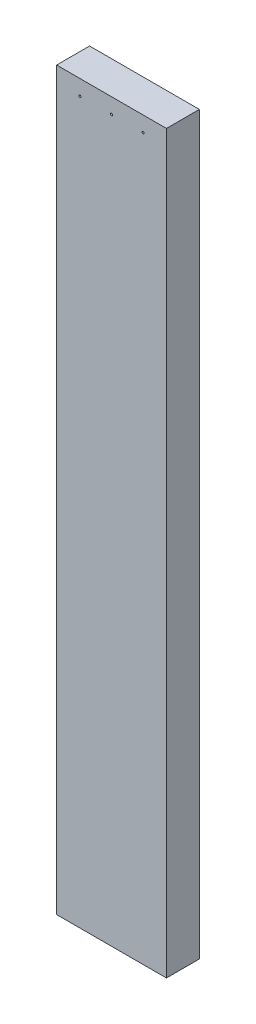
SolidWorks part; units mm, degrees
ref_plane "Front Plane" through (0, 0, 0) normal (0, 0, 1) x (1, 0, 0)
ref_plane "Top Plane" through (0, 0, 0) normal (0, 1, 0) x (1, 0, 0)
ref_plane "Right Plane" through (0, 0, 0) normal (1, 0, 0) x (0, 0, -1)
sketch "Sketch2" plane through (0, 0, 0) normal (0, 1, 0) x (1, 0, 0)
  line L0 (0, 0) -> (63.5, 19.05) construction
  line L1 (0, 0) -> (63.5, 0)
  line L2 (0, 0) -> (0, 19.05)
  line L3 (0, 19.05) -> (63.5, 19.05)
  line L4 (63.5, 0) -> (63.5, 19.05)
  circle A0 centre (31.75, 9.525) radius 3.9335 construction
  point P5 (31.75, 9.525)
  point P8 (0, 0)
  dimension "D1" = 63.5
  dimension "D2" = 19.05
extrude "Boss-Extrude1" add sketch "Sketch2" along normal blind 425.45
sketch "Sketch3" plane through (0, 0, 0) normal (0, -1, 0) x (1, 0, 0)
  line L0 (13.4874, -9.525) -> (50.0126, -9.525) construction
  circle A0 centre (13.4874, -9.525) radius 3.2004 construction
  circle A1 centre (13.4874, -9.525) radius 3.2004 construction
  circle A2 centre (13.4874, -9.525) radius 0.635
  circle A3 centre (31.75, -9.525) radius 0.635
  circle A4 centre (50.0126, -9.525) radius 0.635
  point P3 (31.75, -9.525)
  dimension "D1" = 1.27
extrude "Cut-Extrude1" cut sketch "Sketch3" against normal blind 50.8 and the other way through all
sketch "Sketch4" plane through (0, 0, 0) normal (0, 0, 1) x (1, 0, 0)
  line L0 (13.4366, 416.56) -> (31.7246, 416.56) construction
  line L2 (63.5, 425.45) -> (63.5, 0) construction
  line L5 (31.7246, 416.56) -> (31.7246, 396.9743) construction
  line L6 (31.7246, 416.56) -> (50.0126, 416.56) construction
  line L7 (0, 425.45) -> (63.5, 425.45) construction
  line L9 (50.0126, 0) -> (50.0126, 416.56) construction
  circle A1 centre (31.7246, 416.56) radius 0.635
  circle A3 centre (50.0126, 416.56) radius 0.635
  circle A4 centre (13.4366, 416.56) radius 0.635
  point P2 (12.6946, 416.56)
  point P18 (50.0126, 0)
  dimension "D2" = 1.27
  dimension "D3" = 18.288
  dimension "D1" = 8.89
extrude "Cut-Extrude2" cut sketch "Sketch4" against normal through all
